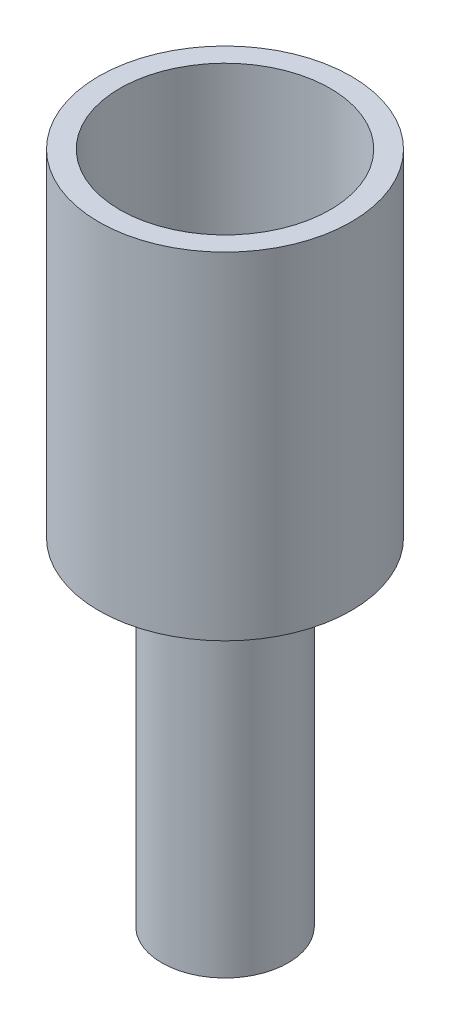
SolidWorks part; units mm, degrees
material "6061-T4 (SS)"
ref_plane "Front Plane" through (0, 0, 0) normal (0, 0, 1) x (1, 0, 0)
ref_plane "Top Plane" through (0, 0, 0) normal (0, 1, 0) x (1, 0, 0)
ref_plane "Right Plane" through (0, 0, 0) normal (1, 0, 0) x (0, 0, -1)
sketch "Sketch1" plane through (0, 0, 0) normal (0, 0, 1) x (1, 0, 0)
  line L0 (-9.525, 25.4) -> (-9.525, 0)
  line L1 (-9.525, 0) -> (-4.7625, 0)
  line L2 (-4.7625, 0) -> (-4.7625, -25.4)
  line L3 (0, -15.8578) -> (0, 15.6451) construction
  dimension "D1" = 9.525
  dimension "D2" = 19.05
  dimension "D3" = 25.4
  dimension "D4" = 25.4
sketch "Sketch2" plane through (0, 0, 0) normal (0, 1, 0) x (1, 0, 0)
  circle A0 centre (0, 0) radius 9.525
  circle A1 centre (0, 0) radius 4.7625
extrude "Boss-Extrude1" add sketch "Sketch2" along normal up to vertex (25.4 mm away) contours A0 A1 | A1 | A1 | A0 region at (-9.2556, 0, 0) region at (0, 0, 0) up to point (-9.525, 25.4, 0)
extrude "Boss-Extrude2" add sketch "Sketch2<3>" against normal up to vertex (25.4 mm away) contours A1 region at (0, 0, 0) up to point (-4.7625, -25.4, 0)
sketch "Sketch2<3>" plane through (0, 0, 0) normal (0, 1, 0) x (1, 0, 0) same geometry as "Sketch2"
sketch "Sketch7" plane through (0, 25.4, 0) normal (0, 1, 0) x (1, 0, 0)
  point P0 (0, 0)
hole_wizard "5/8 (0.625) Diameter Hole1" positions "Sketch7" profile "Sketch6" hole size "5/8" standard "ANSI Inch"
sketch "Sketch6" plane through (0, 25.4, 0) normal (1, 0, 0) x (0, 0, 1)
  line L0 (0, 0) -> (0, 25.4)
  line L1 (0, 25.4) -> (7.9375, 20.6307)
  line L2 (7.9375, 20.6307) -> (7.9375, 0)
  line L5 (7.9375, 0) -> (0, 0)
  line L10 (0, 25.4) -> (-7.9375, 20.6307) construction
  line L11 (0, -6.35) -> (0, 107.95) construction
  dimension "Hole Dia." = 15.875
  dimension "Hole Depth" = 25.4
  dimension "Drill Angle" = 118
sketch "Sketch10" plane through (0, -25.4, 0) normal (0, -1, 0) x (-1, 0, 0)
  point P0 (0, 0)
hole_wizard "1/4 (0.25) Diameter Hole1" positions "Sketch10" profile "Sketch11" hole size "1/4" standard "ANSI Inch" end condition through all
sketch "Sketch11" plane through (0, -25.4, 0) normal (1, 0, 0) x (0, 0, -1)
  line L0 (0, 0) -> (0, 50.8)
  line L1 (0, 50.8) -> (3.175, 50.8)
  line L2 (3.175, 50.8) -> (3.175, 0)
  line L5 (3.175, 0) -> (0, 0)
  line L11 (0, -6.35) -> (0, 107.95) construction
  dimension "Thru Hole Dia." = 6.35
  dimension "Thru Hole Depth" = 50.8
